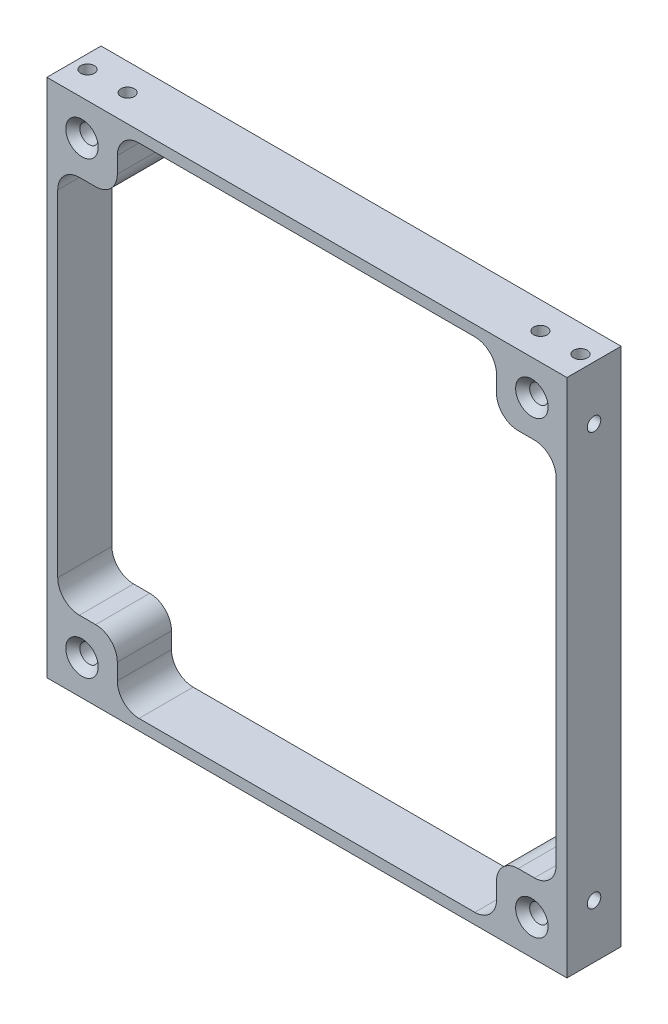
SolidWorks part; units mm, degrees
material "7075-T6 (SN)"
ref_plane "Front Plane" through (0, 0, 0) normal (0, 0, 1) x (1, 0, 0)
ref_plane "Top Plane" through (0, 0, 0) normal (0, 1, 0) x (1, 0, 0)
ref_plane "Right Plane" through (0, 0, 0) normal (1, 0, 0) x (0, 0, -1)
sketch "Construction Lines" plane through (0, 0, 0) normal (0, 0, 1) x (1, 0, 0)
  line L0 (0, 0) -> (0, -14.7163) construction
  line L1 (0, 0) -> (23.9312, 0) construction
sketch "Sketch3" plane through (0, 0, 0) normal (0, 0, 1) x (1, 0, 0)
  line L0 (0, 48) -> (48, 48)
  line L1 (0, 200000) -> (0, -200014.7163) construction
  line L2 (48, 48) -> (48, 0)
  line L3 (-200000, 0) -> (200023.9312, 0) construction
  line L4 (0, 46) -> (31, 46)
  line L5 (46, 31) -> (46, 0)
  line L6 (0, 48) -> (0, 46)
  line L7 (48, 0) -> (46, 0)
  line L8 (35, 42) -> (35, 39)
  line L9 (39, 35) -> (42, 35)
  line L11 (0, 46) -> (46, 46) construction
  line L12 (46, 46) -> (46, 0) construction
  arc A0 (31, 46) -> (35, 42) centre (31, 42) cw
  arc A1 (35, 39) -> (39, 35) centre (39, 39) ccw
  arc A2 (46, 31) -> (42, 35) centre (42, 31) ccw
  dimension "D6" = 4
  dimension "D1" = 48
  dimension "D2" = 48
  dimension "D4" = 13
  dimension "D5" = 13
  dimension "D3" = 2
extrude "BottomLayer" add sketch "Sketch3" along normal blind 10
sketch "TopHolePosition" plane through (0, 0, 10) normal (0, 0, 1) x (1, 0, 0)
  line L0 (0, 0) -> (48, 48) construction
sketch "HolePosition" plane through (0, 0, 10) normal (0, 0, 1) x (1, 0, 0)
  line L0 (0, 41.525) -> (41.525, 41.525) construction
  line L1 (0, 200000) -> (0, -200014.7163) construction
  line L2 (0, 0) -> (48, 48) construction
  line L3 (41.525, 41.525) -> (41.525, 0) construction
  line L4 (-200000, 0) -> (200023.9312, 0) construction
  dimension "D1" = 41.525
hole_wizard "M3 Clearance Hole1" positions "Sketch13" profile "Sketch14" hole size "M3" standard "ISO" end condition through all
sketch "Sketch13" plane through (0, 0, 10) normal (0, 0, 1) x (1, 0, 0)
  point P0 (41.525, 41.525)
sketch "Sketch14" plane through (41.525, 41.525, 10) normal (1, 0, 0) x (0, -1, 0)
  line L0 (0, 0) -> (0, 10)
  line L1 (0, 10) -> (1.7, 10)
  line L2 (1.7, 10) -> (1.7, 1.3)
  line L3 (1.7, 1.3) -> (3, 0)
  line L5 (3, 0) -> (0, 0)
  line L6 (-1.7, 1.3) -> (-3, 0) construction
  line L11 (0, -6.35) -> (0, 107.95) construction
  dimension "Thru Hole Dia." = 3.4
  dimension "Thru Hole Depth" = 10
  dimension "Near C'Sink Dia." = 6
  dimension "Near C'Sink Angle" = 90
ref_axis "Axis1" through (0, 0, -0.5) along (0, 0, 1)
pattern_circular "CirPattern1" count 4 every 90 about axis through (0, 0, -0.5) along (0, 0, 1) of "BottomLayer", "M3 Clearance Hole1"
sketch "SidePlate Hole ZY" plane through (48, 0, 0) normal (1, 0, 0) x (0, 0, -1)
  line L0 (-5, 48) -> (-5, -48) construction
  line L1 (-10, 48) -> (0, 48) construction
  line L2 (-10, -48) -> (0, -48) construction
  line L3 (-10, 38.1) -> (-5, 38.1) construction
  line L5 (-10, -48) -> (-10, 48) construction
  point P8 (-10, 38.1)
  dimension "D1" = 9.9
sketch "SidePlate&RailHole ZX" plane through (0, 48, 0) normal (0, 1, 0) x (1, 0, 0)
  line L0 (48, -5) -> (-48, -5) construction
  line L1 (-48, -10) -> (-48, 0) construction
  line L2 (45.5, -10) -> (45.5, -5) construction
  line L3 (48, -10) -> (-48, -10) construction
  line L7 (38.1, -10) -> (38.1, -5) construction
  line L8 (48, -10) -> (48, 0) construction
  point P7 (45.5, -10)
  point P14 (38.1, -10)
  dimension "D1" = 2.5
  dimension "D2" = 9.9
hole_wizard "Tap Drill M3 Side Plate" positions "Sketch20" profile "Sketch21" hole size "M3" standard "ISO"
sketch "Sketch20" plane through (48, 0, 0) normal (1, 0, 0) x (0, 0, -1)
  point P0 (-5, 38.1)
sketch "Sketch21" plane through (48, 38.1, 5) normal (0, 1, 0) x (0, 0, -1)
  line L0 (0, 0) -> (0, 5.7511)
  line L1 (0, 5.7511) -> (1.25, 5)
  line L2 (1.25, 5) -> (1.25, 0)
  line L5 (1.25, 0) -> (0, 0)
  line L10 (0, 5.7511) -> (-1.25, 5) construction
  line L11 (0, -6.35) -> (0, 107.95) construction
  dimension "Hole Dia." = 2.5
  dimension "Hole Depth" = 5
  dimension "Drill Angle" = 118
hole_wizard "Tap Drill M3 Side Plate " positions "Sketch26" profile "Sketch27" hole size "M3" standard "ISO"
sketch "Sketch26" plane through (0, 48, 0) normal (0, 1, 0) x (1, 0, 0)
  point P0 (38.1, -5)
sketch "Sketch27" plane through (38.1, 48, 5) normal (1, 0, 0) x (0, 0, 1)
  line L0 (0, 0) -> (0, 5.7511)
  line L1 (0, 5.7511) -> (1.25, 5)
  line L2 (1.25, 5) -> (1.25, 0)
  line L5 (1.25, 0) -> (0, 0)
  line L10 (0, 5.7511) -> (-1.25, 5) construction
  line L11 (0, -6.35) -> (0, 107.95) construction
  dimension "Hole Dia." = 2.5
  dimension "Hole Depth" = 5
  dimension "Drill Angle" = 118
hole_wizard "Tap Drill M3 Rail" positions "Sketch28" profile "Sketch29" hole size "M3" standard "ISO"
sketch "Sketch28" plane through (0, 48, 0) normal (0, 1, 0) x (1, 0, 0)
  point P0 (45.5, -5)
sketch "Sketch29" plane through (45.5, 48, 5) normal (1, 0, 0) x (0, 0, 1)
  line L0 (0, 0) -> (0, 5.7511)
  line L1 (0, 5.7511) -> (1.25, 5)
  line L2 (1.25, 5) -> (1.25, 0)
  line L5 (1.25, 0) -> (0, 0)
  line L10 (0, 5.7511) -> (-1.25, 5) construction
  line L11 (0, -6.35) -> (0, 107.95) construction
  dimension "Hole Dia." = 2.5
  dimension "Hole Depth" = 5
  dimension "Drill Angle" = 118
mirror "SidePlate and Rail Holes 1" about plane through (0, 0, 0) normal (1, 0, 0) of "Tap Drill M3 Side Plate", "Tap Drill M3 Rail", "Tap Drill M3 Side Plate "
mirror "Side Plate and Rail Holes 2" about plane through (0, 0, 0) normal (0, 1, 0) of "SidePlate and Rail Holes 1"
